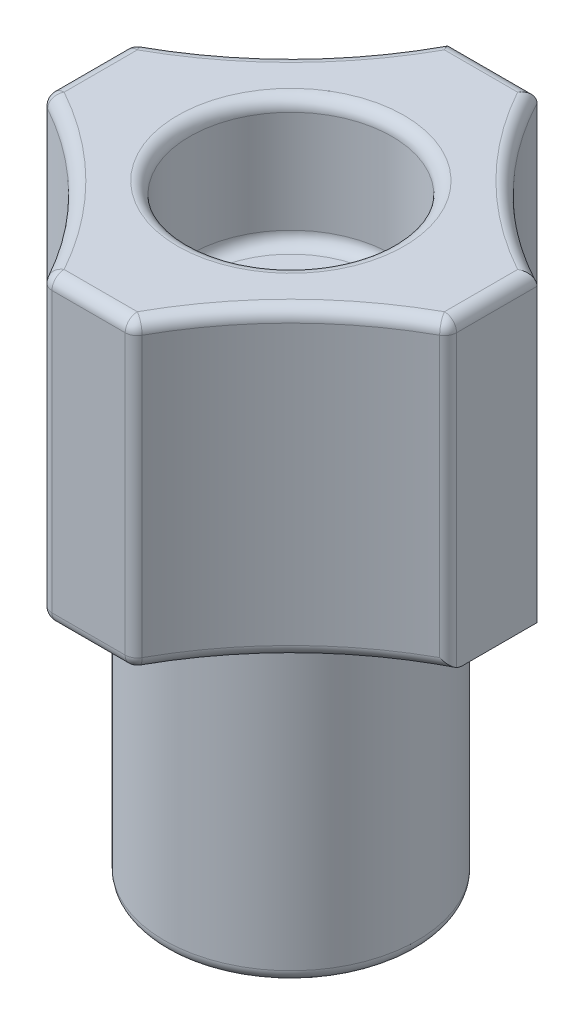
SolidWorks part; units mm, degrees
ref_plane "Front" through (0, 0, 0) normal (0, 0, 1) x (1, 0, 0)
ref_plane "Top" through (0, 0, 0) normal (0, 1, 0) x (1, 0, 0)
ref_plane "Right" through (0, 0, 0) normal (1, 0, 0) x (0, 0, -1)
sketch "Sketch1" plane through (0, 0, 0) normal (0, 1, 0) x (1, 0, 0)
  line L1 (-6.35, 6.35) -> (6.35, 6.35)
  line L2 (-6.35, 6.35) -> (-6.35, -6.35)
  line L3 (-6.35, -6.35) -> (6.35, -6.35)
  line L4 (6.35, 6.35) -> (6.35, -6.35)
  line L5 (-6.35, 6.35) -> (6.35, -6.35) construction
  line L6 (-6.35, -6.35) -> (6.35, 6.35) construction
  point P0 (0, 0)
  dimension "D1" = 12.7
extrude "Boss-Extrude1" add sketch "Sketch1" along normal blind 9.525
sketch "Sketch3" plane through (0, 9.525, 0) normal (0, 1, 0) x (1, 0, 0)
  line L0 (0, 0) -> (0, 50.8) construction
  line L1 (0, 0) -> (50.8, 0) construction
  circle A0 centre (11.9062, 11.9062) radius 11.9062
  dimension "D2" = 23.8125
  dimension "D1" = 50.8
extrude "Cut-Extrude1" cut sketch "Sketch3" against normal through all
ref_axis "Axis1" through (0, 50, 0) along (0, -1, 0)
pattern_circular "CirPattern1" count 4 over 360 about axis through (0, 50, 0) along (0, -1, 0) of "Cut-Extrude1"
sketch "Sketch4" plane through (0, 0, 0) normal (0, -1, 0) x (1, 0, 0)
  circle A0 centre (0, 0) radius 3.9688
  dimension "D1" = 7.9375
extrude "Boss-Extrude2" add sketch "Sketch4" along normal blind 9.525
sketch "Sketch5" plane through (0, 9.525, 0) normal (0, 1, 0) x (1, 0, 0)
  circle A0 centre (0, 0) radius 1.5875
  dimension "D1" = 3.175
extrude "Cut-Extrude2" cut sketch "Sketch5" against normal through all
sketch "Sketch6" plane through (0, 9.525, 0) normal (0, 1, 0) x (1, 0, 0)
  circle A0 centre (0, 0) radius 3.175
  dimension "D1" = 6.35
extrude "Cut-Extrude3" cut sketch "Sketch6" against normal blind 3.9688
fillet "Fillet3" radius 0.381 23 edges at (0, 9.525, 3.175) (0, 5.5563, 3.175) (0, 5.5563, 1.5875) (0, -9.525, 1.5875) (0, -9.525, -3.9688) (-3.4873, 9.525, -3.4873) (-6.35, 4.7625, -1.376) (-3.4873, 0, 3.4873) (-3.4873, 9.525, 3.4873) (-1.376, 4.7625, 6.35) (-6.35, 4.7625, 1.376) (3.4873, 9.525, 3.4873) (3.4873, 0, 3.4873) (1.376, 4.7625, 6.35) (6.35, 4.7625, 1.376) (3.4873, 9.525, -3.4873) (-6.35, 0, 0) (0, 0, 6.35) (6.35, 9.525, 0) (0, 9.525, -6.35) (-6.35, 9.525, 0) (0, 9.525, 6.35) (0, 0, 3.9688)
